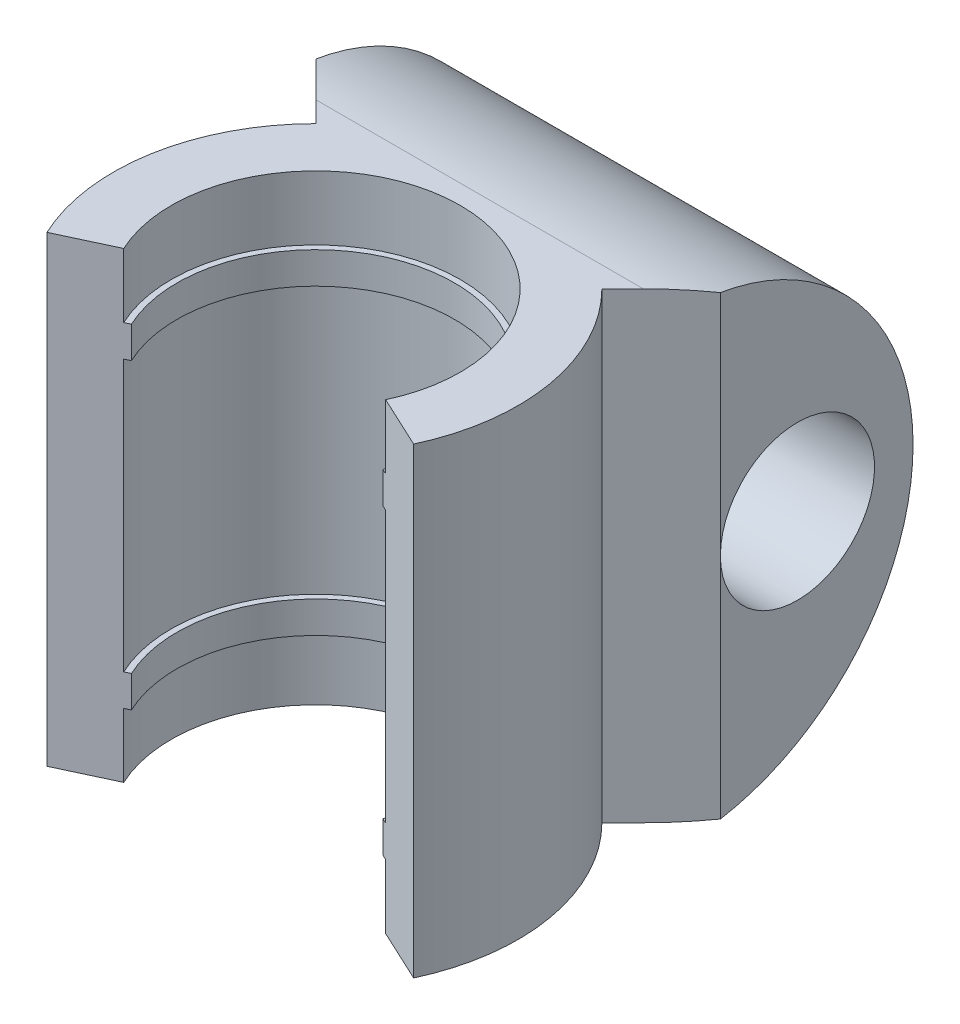
SolidWorks part; units mm, degrees
ref_plane "Front Plane" through (0, 0, 0) normal (0, 0, 1) x (1, 0, 0)
ref_plane "Top Plane" through (0, 0, 0) normal (0, 1, 0) x (1, 0, 0)
ref_plane "Right Plane" through (0, 0, 0) normal (1, 0, 0) x (0, 0, -1)
sketch "Sketch1" plane through (0, 0, 0) normal (1, 0, 0) x (0, 0, -1)
  line L0 (0, -542.9016) -> (0, 26602.1806) construction
  line L1 (7.5, 24) -> (7.5, 20.67)
  line L2 (0, 0) -> (10.5, 0)
  line L3 (0, 0) -> (0, 24) construction
  line L4 (0, 24) -> (10.5, 24)
  line L5 (10.5, 0) -> (10.5, 24)
  line L6 (7.5, 3.33) -> (7.5, 0)
  line L7 (7.5, 3.33) -> (7.2, 3.33)
  line L9 (7.5, 4.97) -> (7.2, 4.97)
  line L10 (7.2, 3.33) -> (7.2, 4.97)
  line L11 (7.5, 20.67) -> (7.2, 20.67)
  line L13 (7.5, 19.03) -> (7.2, 19.03)
  line L14 (7.2, 20.67) -> (7.2, 19.03)
  line L15 (7.5, 19.03) -> (7.5, 4.97)
  dimension "D1" = 7.5
  dimension "D2" = 3
  dimension "D3" = 24
  dimension "D4" = 3.33
  dimension "D5" = 1.64
  dimension "D6" = 0.3
  dimension "D7" = 3.33
revolve "Revolve1" add sketch "Sketch1" angle 230 mid plane about L0 region at (0, 12, -8.9778)
sketch "Sketch2" plane through (0, 24, 0) normal (0, 1, 0) x (1, 0, 0)
  line L0 (-10.5, 10.5) -> (10.5, 10.5) construction
  line L1 (10.5, 10.5) -> (10.5, 20.5)
  line L2 (10.5, 20.5) -> (-10.5, 20.5)
  line L3 (-10.5, 20.5) -> (-10.5, 10.5)
  line L4 (-10.5, 10.5) -> (-7.4246, 7.4246)
  line L5 (10.5, 10.5) -> (7.4246, 7.4246)
  arc A1 (9.5162, -4.4375) -> (-9.5162, -4.4375) centre (0, 0) ccw construction
  arc A2 (7.4246, 7.4246) -> (-7.4246, 7.4246) centre (0, 0) ccw
  arc M7 (9.5162, -4.4375) -> (-9.5162, -4.4375) centre (0, 0) ccw
  dimension "D1" = 10
  dimension "D2" = 45
extrude "Boss-Extrude1" add sketch "Sketch2" against normal up to surface (24 mm away) contours L3 L0 L1 L2 | L0 L5 M7 | L0 L4 A2 region at (0, 24, -15.5) region at (-6.7555, 24, -9.5538) region at (6.7555, 24, -9.5538) up to face at (0, 0, -2.5982)
fillet "Fillet1" radius 12 2 edges at (0, 0, -20.5) (0, 24, -20.5)
sketch "Sketch3" plane through (-10.5, 0, 0) normal (-1, 0, 0) x (0, 0, 1)
  line L1 (-10.5, 0.1678) -> (-10.5, 23.8322) construction
  circle A0 centre (-14.5, 12) radius 4
  point P2 (0, 0)
  point P3 (0, 0)
  point P4 (-14.5685, 12)
  point P6 (0, 0)
  point P7 (0, 0)
  dimension "D1" = 8
extrude "Cut-Extrude1" cut sketch "Sketch3" against normal through all contours A0
